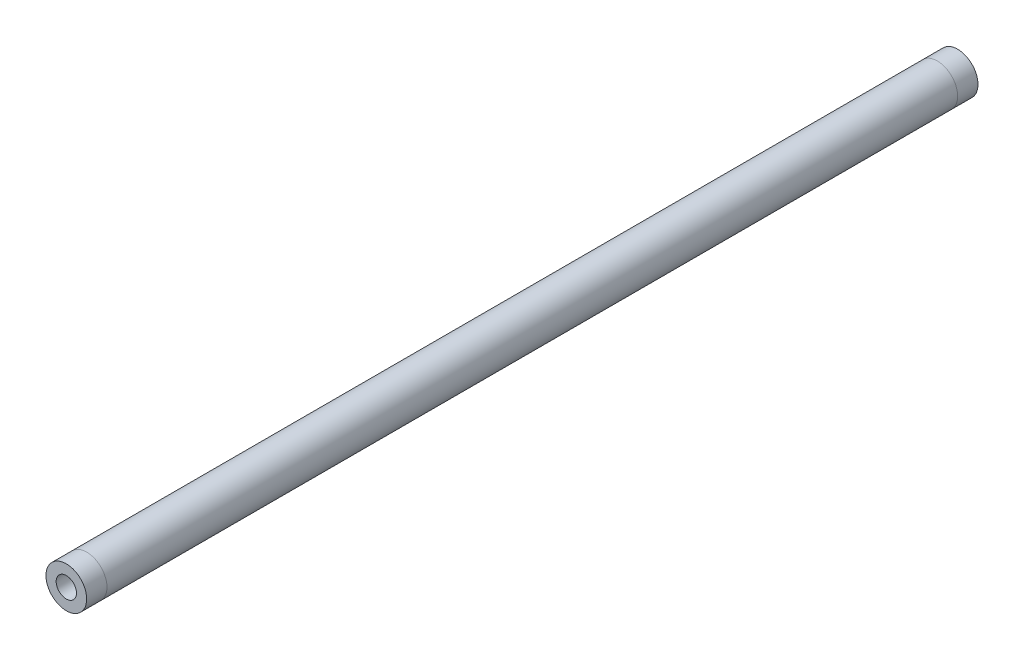
SolidWorks part; units mm, degrees
material "AISI 4130 Steel, normalized at 870C"
ref_plane "Front Plane" through (0, 0, 0) normal (0, 0, 1) x (1, 0, 0)
ref_plane "Top Plane" through (0, 0, 0) normal (0, 1, 0) x (1, 0, 0)
ref_plane "Right Plane" through (0, 0, 0) normal (1, 0, 0) x (0, 0, -1)
sketch "Axis" plane through (0, 0, 0) normal (0, 1, 0) x (1, 0, 0)
  line L0 (0, 0) -> (0, 21.9075) construction
  line L1 (0, 21.9075) -> (0, 300.0818) construction
  line L2 (0, 300.0818) -> (0, 321.9893) construction
  dimension "D1" = 21.9075
  dimension "D2" = 321.9893
sketch "Sketch2" plane through (0, 0, 0) normal (0, 0, 1) x (1, 0, 0)
  circle A0 centre (0, 0) radius 6.35
  circle A1 centre (0, 0) radius 3.175
  circle A2 centre (0, 0) radius 4.7625
  dimension "D1" = 12.7
  dimension "D2" = 6.35
  dimension "D3" = 9.525
extrude "Threaded Insert 1-1" add sketch "Sketch2" against normal blind 6.35 from vertex contours A0 A2 | A2 A1 region at (-6.1704, 0, 0) region at (-4.6278, 0, 0) starting at point (0, 0, -21.9075)
extrude "Threaded Insert 1-2" add sketch "Sketch2<5>" against normal blind 9.525 from surface contours A2 A1 region at (-4.6278, 0, 0) starting at face at (6.35, 0, -28.2575)
sketch "Sketch2<5>" plane through (0, 0, 0) normal (0, 0, 1) x (1, 0, 0) same geometry as "Sketch2"
extrude "Boss-Extrude4" add sketch "Sketch2<7>" along normal blind 6.35 from vertex separate body contours A0 A2 | A2 A1 region at (-6.1704, 0, 0) region at (-4.6278, 0, 0) starting at point (0, 0, -300.0818)
sketch "Sketch2<7>" plane through (0, 0, 0) normal (0, 0, 1) x (1, 0, 0) same geometry as "Sketch2"
extrude "Boss-Extrude5" add sketch "Sketch2<8>" along normal blind 9.525 from surface contours A2 A1 region at (-4.6278, 0, 0) starting at face at (6.35, 0, -293.7318)
sketch "Sketch2<8>" plane through (0, 0, 0) normal (0, 0, 1) x (1, 0, 0) same geometry as "Sketch2"
extrude "Boss-Extrude6" add sketch "Sketch2<9>" against normal up to surface (293.7318 mm away) from surface separate body contours A0 A2 region at (-6.1704, 0, 0) up to face at (6.35, 0, -293.7318) starting at face at (4.7625, 0, -28.2575)
sketch "Sketch2<9>" plane through (0, 0, 0) normal (0, 0, 1) x (1, 0, 0) same geometry as "Sketch2"
equation "\"Tube Outer Diameter\"= .5"
equation "\"Tube Inner Diameter\"= .375"
equation "\"Rod end Diameter\"= .25"
equation "\"Threaded Insert Out\"= .25"
equation "\"Threaded Insert In\"= .375'`"
equation "\"D1@Sketch2\"=\"Tube Outer Diameter\""
equation "\"D2@Sketch2\"=\"Rod end Diameter\""
equation "\"D1@Threaded Insert 1-1\" = \"Threaded Insert Out\""
equation "\"D3@Sketch2\"=\"Tube Inner Diameter\""
equation "\"D1@Threaded Insert 1-2\" = \"Threaded Insert In\""
equation "\"D1@Boss-Extrude4\"=\"Threaded Insert Out\""
equation "\"D1@Boss-Extrude5\"=\"Threaded Insert In\""
